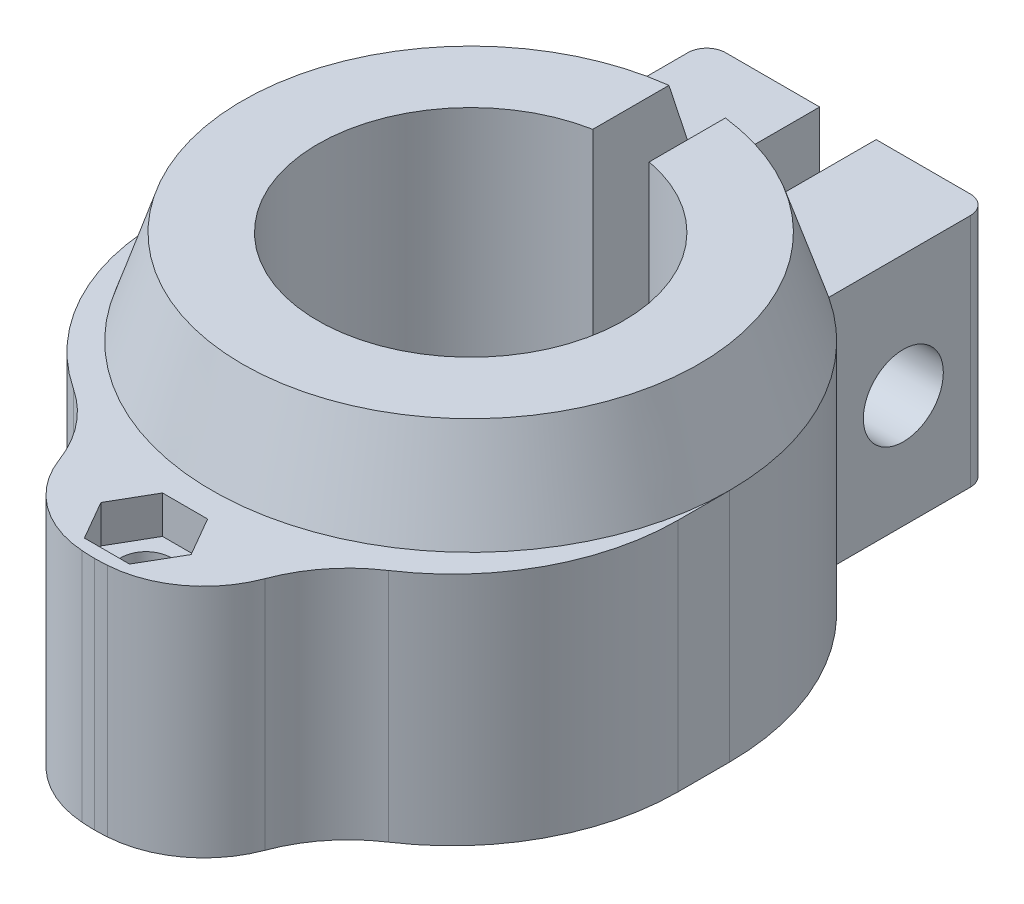
SolidWorks part; units mm, degrees
ref_plane "Front Plane" through (0, 0, 0) normal (0, 0, 1) x (1, 0, 0)
ref_plane "Top Plane" through (0, 0, 0) normal (0, 1, 0) x (1, 0, 0)
ref_plane "Right Plane" through (0, 0, 0) normal (1, 0, 0) x (0, 0, -1)
sketch "Sketch1" plane through (0, 0, 0) normal (0, 0, 1) x (1, 0, 0)
  line L0 (0, 0) -> (0, 58.0235) construction
  line L1 (16.25, 0) -> (40, 0)
  line L2 (40, 0) -> (40, 25)
  line L3 (40, 25) -> (27.5, 25)
  line L4 (27.5, 25) -> (24.25, 35)
  line L5 (24.25, 35) -> (16.25, 35)
  line L6 (16.25, 35) -> (16.25, 0)
  dimension "D1" = 32.5
  dimension "D2" = 80
  dimension "D3" = 25
  dimension "D4" = 35
  dimension "D5" = 55
  dimension "D6" = 8
revolve "Revolve1" add sketch "Sketch1" angle 360 about L0
sketch "Sketch2" plane through (0, 0, 0) normal (0, -1, 0) x (1, 0, 0)
  line L0 (0, 0) -> (0, -15.1778) construction
  line L1 (-3, 0) -> (3, 0)
  line L2 (-3, 0) -> (-3, -60)
  line L3 (-3, -60) -> (3, -60)
  line L4 (3, 0) -> (3, -60)
  dimension "D1" = 6
  dimension "D2" = 60
extrude "Cut-Extrude1" cut sketch "Sketch2" against normal through all
sketch "Sketch3" plane through (-3, 0, 0) normal (1, 0, 0) x (0, 0, -1)
  line L0 (39.8873, 25) -> (27.3359, 25) construction
  line L1 (15.9707, 35) -> (15.9707, 0) construction
  circle A0 centre (30.9707, 12) radius 4.25
  dimension "D1" = 8.5
  dimension "D2" = 13
  dimension "D3" = 15
extrude "Cut-Extrude2" cut sketch "Sketch3" against normal through all and the other way through all
sketch "Sketch6" plane through (0, 0, 0) normal (0, -1, 0) x (1, 0, 0)
  line L0 (0, 0) -> (0, 34.5) construction
  circle A0 centre (0, 34.5) radius 2.65
  dimension "D1" = 5.3
  dimension "D2" = 34.5
extrude "Cut-Extrude5" cut sketch "Sketch6" against normal through all contours A0
sketch "Sketch7" plane through (0, 25, 0) normal (0, 1, 0) x (1, 0, 0)
  line L1 (-2.396, -30.35) -> (-4.792, -34.5)
  line L2 (-4.792, -34.5) -> (-2.396, -38.65)
  line L3 (-2.396, -38.65) -> (2.396, -38.65)
  line L4 (2.396, -38.65) -> (4.792, -34.5)
  line L5 (4.792, -34.5) -> (2.396, -30.35)
  line L6 (2.396, -30.35) -> (-2.396, -30.35)
  circle A0 centre (0, -34.5) radius 4.15 construction
  dimension "D1" = 8.3
extrude "Cut-Extrude6" cut sketch "Sketch7" against normal blind 4
sketch "Sketch8" plane through (0, 25, 0) normal (0, 1, 0) x (1, 0, 0)
  line L0 (-27.5, 0) -> (-27.5, -50)
  line L3 (27.5, 0) -> (27.5, -50)
  line L4 (-27.5, -50) -> (-50, -50)
  line L5 (-50, -50) -> (-50, 70)
  line L6 (-50, 70) -> (50, 70)
  line L7 (50, 70) -> (50, -50)
  line L8 (50, -50) -> (27.5, -50)
  line L9 (-15, 23.0489) -> (-15, 60)
  line L10 (-15, 60) -> (15, 60)
  line L11 (15, 60) -> (15, 23.0489)
  line L13 (0, 0) -> (0, 14.2696) construction
  arc A0 (-3, 27.3359) -> (3, 27.3359) centre (0, 0) ccw construction
  arc A3 (-15, 23.0489) -> (-27.5, 0) centre (0, 0) ccw
  arc A5 (27.5, 0) -> (15, 23.0489) centre (0, 0) ccw
  dimension "D1" = 70
  dimension "D2" = 120
  dimension "D3" = 100
  dimension "D4" = 60
  dimension "D5" = 30
extrude "Cut-Extrude7" cut sketch "Sketch8" against normal through all
fillet "Fillet1" radius 28 2 edges at (27.5, 12.5, 29.0474) (-27.5, 12.5, 29.0474)
sketch "Sketch11" plane through (15, 0, 0) normal (1, 0, 0) x (0, 0, -1)
  circle A0 centre (30.9707, 12) radius 8.5
  dimension "D1" = 17
sketch "Sketch12" plane through (0, 25, 0) normal (0, 1, 0) x (1, 0, 0)
  line L0 (-3, 37.081) -> (-3, 40.081)
  line L1 (-15, 37.081) -> (-3, 37.081)
  line L2 (-15, 37.081) -> (-15, 40.081)
  line L3 (-15, 40.081) -> (-3, 40.081)
  line L4 (15, 37.081) -> (15, 40.081)
  line L5 (-3, 39.8873) -> (-3, 27.3359) construction
  line L6 (3, 37.081) -> (3, 40.081)
  line L7 (3, 27.3359) -> (3, 39.8873) construction
  line L8 (3, 37.081) -> (15, 37.081)
  line L9 (3, 40.081) -> (15, 40.081)
  dimension "D1" = 3
extrude "Boss-Extrude1" add sketch "Sketch12" against normal up to surface (25 mm away) up to face at (0, 0, -9.8957)
chamfer "Chamfer1" distance 0.5 angle 45 1 edges at (0, 0, 16.25)
fillet "Fillet2" radius 2 2 edges at (15, 12.5, -40.081) (-15, 12.5, -40.081)
ref_plane "Plane4" through (0, 15, 0) normal (0, 1, 0) x (1, 0, 0)
sketch "Sketch13" plane through (0, 15, 0) normal (0, 1, 0) x (1, 0, 0)
  circle A0 centre (0, -34.5) radius 4.625
  dimension "D1" = 9.25
extrude "Cut-Extrude8" cut sketch "Sketch13" against normal through all
sketch "Sketch15" plane through (0, 15, 0) normal (0, -1, 0) x (1, 0, 0)
  circle A0 centre (0, 34.5) radius 2.65 construction
  circle A1 centre (0, 34.5) radius 2.65
extrude "Boss-Extrude2" add sketch "Sketch15" against normal blind 0.2
sketch "Sketch16" plane through (0, 25, 0) normal (0, 1, 0) x (1, 0, 0)
  line L0 (0, 0) -> (0, -63.3806) construction
  circle A0 centre (25, -38) radius 15
  circle A1 centre (-25, -38) radius 15
  dimension "D1" = 30
  dimension "D2" = 38
  dimension "D3" = 25
extrude "Cut-Extrude9" cut sketch "Sketch16" against normal through all
fillet "Fillet3" radius 11 2 edges at (-10.0001, 12.5, 37.9462) (10.0001, 12.5, 37.9462)
fillet "Fillet4" radius 24 2 edges at (-25.2435, 12.5, 23.002) (25.2435, 12.5, 23.002)
